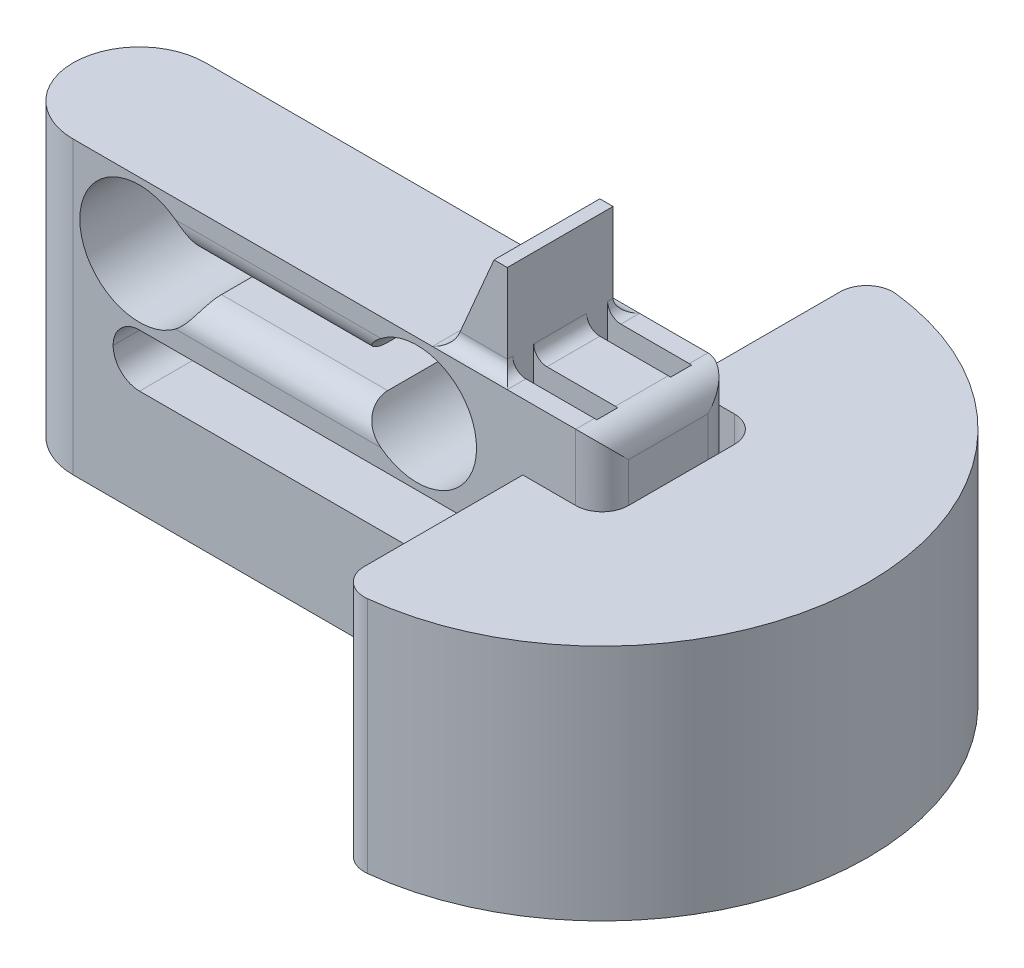
SolidWorks part; units mm, degrees
material "VITON"
ref_plane "Front Plane" through (0, 0, 0) normal (0, 0, 1) x (1, 0, 0)
ref_plane "Top Plane" through (0, 0, 0) normal (0, 1, 0) x (1, 0, 0)
ref_plane "Right Plane" through (0, 0, 0) normal (1, 0, 0) x (0, 0, -1)
other "Center of Mass"
sketch "Sketch1" plane through (0, 0, 0) normal (0, 0, 1) x (1, 0, 0)
  line L0 (5, 0) -> (0, 0)
  line L1 (0, 0) -> (-5, 0)
  line L2 (-5, 0) -> (-35, 0)
  line L3 (5, 0) -> (5, -10)
  line L4 (5, -10) -> (-5, -10)
  line L5 (-5, -10) -> (-31.9826, -10)
  line L6 (-35, 0) -> (-40, 0)
  line L7 (-26.8791, -3.4207) -> (-11.5008, -3.4207)
  line L8 (-26.8791, -3.4207) -> (-26.8791, -6.5793)
  line L9 (-26.8791, -6.5793) -> (-11.5008, -6.5793)
  line L10 (-11.5008, -3.4207) -> (-11.5008, -6.5793)
  line L11 (-26.8791, -3.4207) -> (-11.5008, -6.5793) construction
  line L12 (-26.8791, -6.5793) -> (-11.5008, -3.4207) construction
  line L13 (-40, 0) -> (-40, -14)
  line L14 (-40, -14) -> (-31.9826, -14)
  line L15 (-31.9826, -14) -> (-31.9826, -10)
  circle A0 centre (-30, -5) radius 4.5
  circle A1 centre (-9, -5) radius 4.5
  point P12 (-19.1899, -5)
  dimension "D5" = 5
  dimension "D6" = 5
  dimension "D7" = 9
  dimension "D8" = 9
  dimension "D1" = 5
  dimension "D2" = 5
  dimension "D3" = 30
  dimension "D4" = 10
  dimension "D9" = 4
  dimension "D10" = 40
  dimension "D11" = 14
extrude "Boss-Extrude1" add sketch "Sketch1" along normal blind 5 and the other way blind 5 contours L14 L15 L5 L4 L3 L0 L1 L2 L6 L13 A1 L9 A0 L7 region at (4.5287, -5, 0)
sketch "Sketch2" plane through (0, 0, 0) normal (0, 1, 0) x (1, 0, 0)
  line L1 (-3.175, -3.5875) -> (3.175, -3.5875)
  line L2 (-3.175, -3.5875) -> (-3.175, -2)
  line L3 (-3.175, -2) -> (3.175, -2)
  line L4 (3.175, -3.5875) -> (3.175, -2)
  line L5 (0, -2) -> (0, -3.5875) construction
  line L6 (5, 5) -> (-40, 5) construction
  line L7 (0, 0) -> (3.6499, 0) construction
  line L8 (3.175, 3.5875) -> (3.175, 2)
  line L9 (-3.175, 3.5875) -> (3.175, 3.5875)
  line L10 (-3.175, 3.5875) -> (-3.175, 2)
  line L11 (-3.175, 2) -> (3.175, 2)
  dimension "D1" = 6.35
  dimension "D2" = 7
  dimension "D3" = 1.5875
extrude "Cut-Extrude1" cut sketch "Sketch2" against normal blind 5
sketch "Sketch3" plane through (0, 0, 0) normal (0, 1, 0) x (1, 0, 0)
  line L0 (5, -5) -> (-40, -5) construction
  line L1 (-40, 5) -> (5.8816, 5)
  line L2 (-40, 5) -> (-40, -5)
  line L3 (-40, -5) -> (5.8816, -5)
  line L4 (5.8816, 5) -> (5.8816, -5)
  line L6 (-44.7352, 22.5342) -> (0, 22.5342)
  line L7 (-44.7352, 22.5342) -> (-44.7352, -27.8282)
  line L8 (-44.7352, -27.8282) -> (0, -27.8282)
  line L9 (0, 22.5342) -> (0, -27.8282)
  circle A0 centre (0, 0) radius 20.1
  dimension "D1" = 40.2
extrude "Boss-Extrude2" add sketch "Sketch3" against normal blind 8 from offset 14 contours L9 A0 L1 L4 L3 | L1 L9 L3 L4 | L1 A0 L3 L9 | A0 L1 L2 L3 region at (-29.9445, 0, 0) region at (-9.9463, 0, 0) region at (9.1017, 0, 0) region at (2.9408, 0, 0) offset against normal yes
sketch "Sketch4" plane through (0, -14, 0) normal (0, 1, 0) x (1, 0, 0)
  line L0 (5, 5) -> (-40, 5) construction
  line L1 (0, 20.1) -> (46.8504, 20.1)
  line L2 (0, 20.1) -> (0, -35.9681)
  line L3 (0, -35.9681) -> (46.8504, -35.9681)
  line L4 (46.8504, 20.1) -> (46.8504, -35.9681)
  line L5 (6, 6) -> (-6.1468, 6)
  line L6 (6, 6) -> (6, -6)
  line L7 (6, -6) -> (-6.1468, -6)
  line L8 (-6.1468, 6) -> (-6.1468, -6)
  line L9 (5, -5) -> (-40, -5) construction
  line L10 (5, 5) -> (5, -5) construction
  circle A0 centre (0, 0) radius 20.1
  arc A1 (0, -20.1) -> (0, 20.1) centre (0, 0) ccw construction
  arc M8 (0, -20.1) -> (0, 20.1) centre (0, 0) ccw
  line M9 (0, 20.1) -> (0, 5)
  dimension "D1" = 1
  dimension "D2" = 1
  dimension "D3" = 1
extrude "Boss-Extrude3" add sketch "Sketch4" along normal blind 10 contours L6 L7 L2 L5 M8 M9 region at (9.2385, -14, 0)
fillet "Fillet2" radius 5 2 edges at (-40, -11, -5) (-40, -11, 5)
fillet "Fillet6" radius 2 5 edges at (6, -9, -6) (6, -9, 6) (5, -5, -5) (5, -5, 5) (5, 0, 0)
fillet "Fillet3" radius 2 8 edges at (-19.5, -3.4207, -5) (-19.5, -6.5793, -5) (-19.5, -6.5793, 5) (-19.5, -3.4207, 5) (-31.9826, -10, 0) (-31.9826, -14, 0) (0, -13, -20.1) (0, -13, 20.1)
sketch "Sketch5" plane through (0, -22, 0) normal (0, -1, 0) x (1, 0, 0)
  line L0 (-35, 0) -> (-12, 0) construction
  line L1 (-35, 3.25) -> (-12, 3.25)
  line L2 (-35, -3.25) -> (-12, -3.25)
  line L3 (-6, 0) -> (0, 0) construction
  line L4 (-7.5, 1.5) -> (-4.5, 1.5)
  line L5 (-7.5, 1.5) -> (-7.5, -1.5)
  line L6 (-7.5, -1.5) -> (-4.5, -1.5)
  line L7 (-4.5, 1.5) -> (-4.5, -1.5)
  line L8 (-7.5, 1.5) -> (-4.5, -1.5) construction
  line L9 (-7.5, -1.5) -> (-4.5, 1.5) construction
  line L10 (4.5, 1.5) -> (7.5, 1.5)
  line L11 (4.5, 1.5) -> (4.5, -1.5)
  line L12 (4.5, -1.5) -> (7.5, -1.5)
  line L13 (7.5, 1.5) -> (7.5, -1.5)
  line L14 (4.5, 1.5) -> (7.5, -1.5) construction
  line L15 (4.5, -1.5) -> (7.5, 1.5) construction
  line L16 (0, 0) -> (6, 0) construction
  arc A0 (-35, 3.25) -> (-35, -3.25) centre (-35, 0) ccw
  arc A1 (-12, -3.25) -> (-12, 3.25) centre (-12, 0) ccw
  circle A3 centre (0, 0) radius 1.5
  point P3 (-23.5, 0)
  point P8 (-6, 0)
  point P13 (6, 0)
  dimension "D3" = 3
  dimension "D9" = 3
  dimension "D1" = 35
  dimension "D2" = 12
  dimension "D4" = 3
  dimension "D5" = 0
  dimension "D6" = 12
  dimension "D7" = 3
extrude "Cut-Extrude2" cut sketch "Sketch5" against normal blind 4
fillet "Fillet4" radius 1 6 edges at (-23.5, -18, 3.25) (-8.75, -18, 0) (-23.5, -18, -3.25) (-38.25, -18, 0) (0, -18, -5) (0, -18, 5)
sketch "Sketch6" plane through (0, -22, 0) normal (0, -1, 0) x (1, 0, 0)
  circle A0 centre (-35, 0) radius 3.25
extrude "Cut-Extrude3" cut sketch "Sketch6" against normal blind 5
sketch "Sketch7" plane through (0, 0, 0) normal (0, 1, 0) x (1, 0, 0)
  circle A0 centre (0, 0) radius 2.5
  dimension "D1" = 5
extrude "Boss-Extrude4" add sketch "Sketch7" along normal blind 3.7 from surface starting at face at (-4.0723, -14, 0)
sketch "Sketch9" plane through (0, -10.3, 0) normal (0, 1, 0) x (1, 0, 0)
  circle A0 centre (0, 0) radius 1.45
  dimension "D1" = 2.9
extrude "Cut-Extrude4" cut sketch "Sketch9" against normal blind 4.6 contours A0
fillet "Fillet5" radius 2.5 1 edges at (0, -14, 2.5)
sketch "Sketch10" plane through (0, 0, 0) normal (0, 1, 0) x (1, 0, 0)
  line L0 (-7.175, 0) -> (-3.175, 0) construction
  line L1 (-3.175, 4) -> (-7.175, 4)
  line L2 (-3.175, 4) -> (-3.175, -4)
  line L3 (-3.175, -4) -> (-7.175, -4)
  line L4 (-7.175, 4) -> (-7.175, -4)
  line L6 (-3.175, -2) -> (-3.175, -3.5875) construction
  dimension "D1" = 8
  dimension "D2" = 4
extrude "Boss-Extrude5" add sketch "Sketch10" along normal blind 7
sketch "Sketch11" plane through (0, 0, 4) normal (0, 0, 1) x (1, 0, 0)
  line L0 (-7.175, 0) -> (-7.175, 7)
  line L1 (-7.175, 7) -> (-3.175, 7) construction
  line L2 (-7.175, 7) -> (-7.175, 0) construction
  line L3 (-7.175, 7) -> (-4.175, 7)
  line L4 (-4.175, 7) -> (-7.175, 0)
  dimension "D1" = 3
extrude "Cut-Extrude5" cut sketch "Sketch11" against normal up to next contours L4 L0 L3
fillet "Fillet7" radius 1 6 edges at (-3.175, 0, 3.7938) (-3.175, 0, -3.7938) (-5.175, 0, -4) (-5.175, 0, 4) (-7.175, 0, 0) (-3.175, 0, 0)
